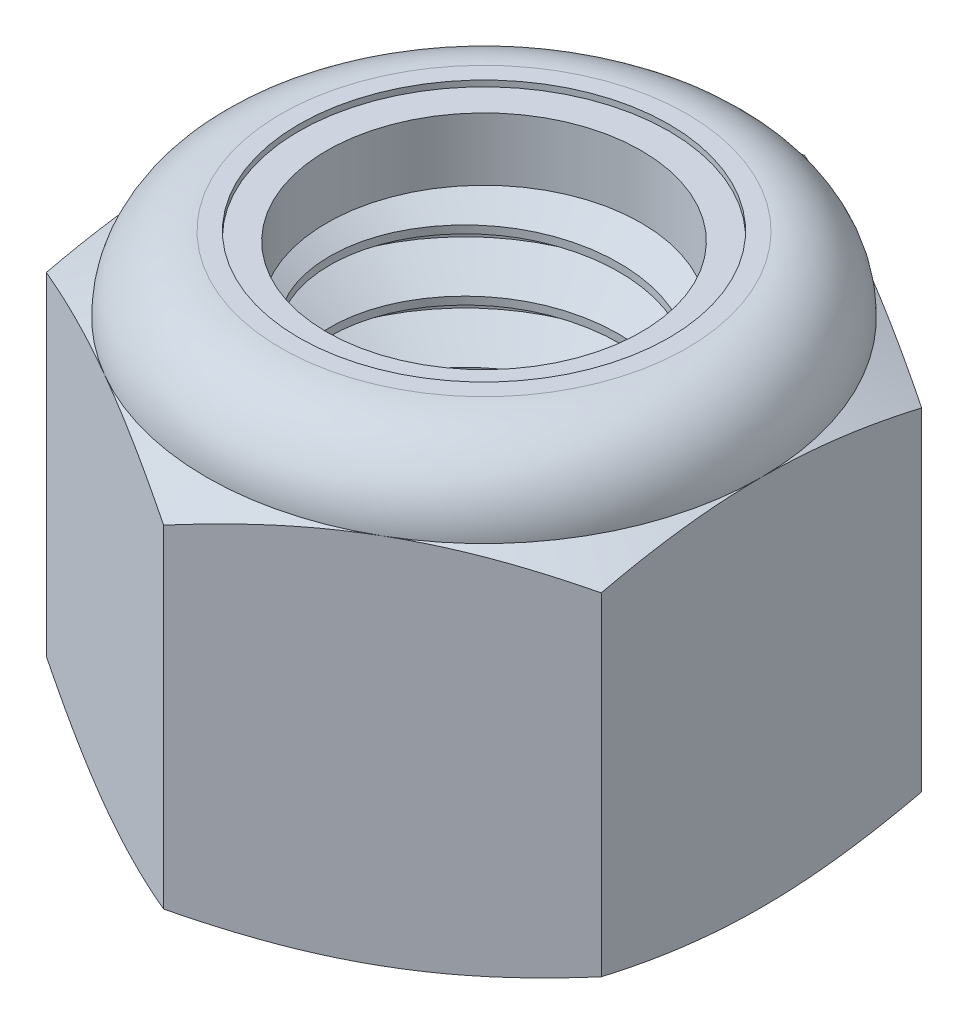
SolidWorks part; units mm, degrees
note: '?' marks a value the reader was unsure of.
ref_plane "Front" through (0, 0, 0) normal (0, 0, 1) x (1, 0, 0)
ref_plane "Top" through (0, 0, 0) normal (0, 1, 0) x (1, 0, 0)
ref_plane "Right" through (0, 0, 0) normal (1, 0, 0) x (0, 0, -1)
sketch "Sketch8" plane through (0, 0, 0) normal (1, 0, 0) x (0, 0, -1)
  line L0 (0, 0) -> (0, 11.5094) construction
  line L1 (7.1437, 0) -> (-7.1437, 0) construction
  line L2 (-4.7625, 11.5094) -> (4.7625, 11.5094) construction
  line L3 (4.7625, 11.5094) -> (4.7625, 9.9219) construction
sketch "Sketch1" plane through (0, 0, 0) normal (0, 1, 0) x (1, 0, 0)
  line L1 (0, 8.2489) -> (-7.1438, 4.1244)
  line L2 (-7.1438, 4.1244) -> (-7.1437, -4.1244)
  line L3 (-7.1437, -4.1244) -> (0, -8.2489)
  line L4 (0, -8.2489) -> (7.1438, -4.1244)
  line L5 (7.1438, -4.1244) -> (7.1438, 4.1244)
  line L6 (7.1438, 4.1244) -> (0, 8.2489)
  circle A0 centre (0, 0) radius 7.1438 construction
  circle A1 centre (0, 0) radius 4.7625
extrude "Extrude1" add sketch "Sketch1" along normal up to vertex (11.5094 mm away) up to point (0, 11.5094, 0)
sketch "Sketch5" plane through (0, 0, 0) normal (1, 0, 0) x (0, 0, -1)
  line L0 (0, 0) -> (7.1437, 0)
  line L1 (7.1437, 0) -> (8.2489, 0.5153)
  line L2 (8.2489, 0.5153) -> (8.2489, 9.0758)
  line L3 (8.2489, 9.0758) -> (7.1437, 9.5911)
  line L4 (5.2255, 11.5094) -> (5.2255, 12.7794)
  line L5 (5.2255, 12.7794) -> (9.5189, 12.7794)
  line L6 (9.5189, 12.7794) -> (9.5189, -1.27)
  line L7 (9.5189, -1.27) -> (0, -1.27)
  line L8 (0, -1.27) -> (0, 0)
  line L9 (7.1437, 9.5911) -> (7.1437, 0) construction
  line L12 (8.2489, 11.5094) -> (8.2489, 0) construction
  line L13 (8.2489, 5.7547) -> (9.5189, 5.7547) construction
  line L15 (0, 0) -> (0, 12.7794) construction
  line L18 (7.1437, 0) -> (-7.1437, 0) construction
  line L19 (4.1244, 11.5094) -> (8.2489, 11.5094) construction
  line L20 (0, 12.7794) -> (5.2255, 12.7794) construction
  line L21 (4.1244, 0) -> (8.2489, 0) construction
  arc A0 (7.1437, 9.5911) -> (5.2255, 11.5094) centre (5.2255, 9.5911) ccw
  dimension "D1" = 25
  dimension "D2" = 1.27
  dimension "D4" = 1.9182
revolve "Cut-Revolve3" cut sketch "Sketch5" angle 360 about L15
sketch "Sketch4" plane through (0, 0, 0) normal (1, 0, 0) x (0, 0, -1)
  line L0 (0, 9.5911) -> (5.2388, 9.5911)
  line L1 (5.2388, 9.5911) -> (0, 7.1483)
  line L3 (0, 2.4429) -> (5.2388, 0)
  line L4 (5.2388, 0) -> (0, 0)
  line L5 (0, 0) -> (0, 9.5911) construction
  line L10 (0, 0) -> (0, 11.5094) construction
  line L11 (0, 2.4429) -> (0, 0)
  line L12 (0, 9.5911) -> (0, 7.1483)
  line L13 (6.1867, 9.5911) -> (0, 9.5911) construction
  dimension "D1" = 25
  dimension "D2" = 10.4775
sketch "Sketch6" plane through (0, 0, 0) normal (1, 0, 0) x (0, 0, -1)
  line L0 (0, 9.5911) -> (6.9913, 9.5911)
  line L1 (5.2255, 11.357) -> (2.6128, 11.357)
  line L2 (0, 12.7794) -> (0, 9.5911)
  line L3 (2.6128, 12.7794) -> (0, 12.7794)
  line L4 (0, 12.7794) -> (5.2255, 12.7794) construction
  line L5 (0, 0) -> (0, 12.7794) construction
  line L6 (0, 12.7794) -> (0, 0) construction
  line L7 (2.6128, 11.357) -> (2.6128, 12.7794)
  line L8 (5.2255, 11.5094) -> (5.2255, 11.357) construction
  line L9 (2.6128, 11.357) -> (0, 11.357) construction
  line L10 (0, 11.357) -> (0, 7.1483) construction
  arc A0 (6.9913, 9.5911) -> (5.2255, 11.357) centre (5.2255, 9.5911) ccw
  arc A1 (7.1437, 9.5911) -> (5.2255, 11.5094) centre (5.2255, 9.5911) ccw construction
  dimension "D1" = 0.1524
revolve "Cut-Revolve4" cut sketch "Sketch6" angle 360 about L6
revolve "Cut-Revolve2" cut sketch "Sketch4" angle 360 about L5
sketch "Sketch7" plane through (0, 0, 0) normal (1, 0, 0) x (0, 0, -1)
  line L0 (4.0481, 9.6673) -> (6.9134, 9.6673)
  line L1 (5.2255, 11.2808) -> (4.0481, 11.2808)
  line L2 (4.0481, 11.2808) -> (4.0481, 9.6673)
  line L3 (4.0481, 9.6673) -> (0, 9.6673) construction
  line L4 (0, 9.6673) -> (0, 11.2808) construction
  line L5 (0, 11.2808) -> (4.0481, 11.2808) construction
  line L6 (4.0481, 9.6673) -> (4.0481, 9.5911) construction
  line L7 (0, 9.5911) -> (6.9913, 9.5911) construction
  line L8 (5.2255, 11.2808) -> (5.2255, 11.357) construction
  arc A0 (6.9134, 9.6673) -> (5.2255, 11.2808) centre (5.2255, 9.5911) ccw
  arc A2 (6.9913, 9.5911) -> (5.2255, 11.357) centre (5.2255, 9.5911) ccw construction
  dimension "D1" = 0.0762
  dimension "D2" = 8.0963
revolve "Revolve2" add sketch "Sketch7" angle 360 about L4
sketch "Sketch2" plane through (0, 0, 0) normal (1, 0, 0) x (0, 0, -1)
  line L0 (-4.7625, 0) -> (-4.7625, 9.5911) construction
  line L1 (0, 0) -> (4.7625, 0)
  line L2 (0, 0) -> (0, 9.5911)
  line L3 (0, 9.5911) -> (4.7625, 9.5911)
  line L4 (4.7625, 0) -> (4.7625, 9.5911)
  line L6 (6.1867, 9.5911) -> (7.1437, 9.5911) construction
  line L7 (0, -4.7625) -> (0, 0) construction
revolve "Revolve1" add sketch "Sketch2" angle 360 about L7
sketch "Sketch9" plane through (0, 0, 0) normal (1, 0, 0) x (0, 0, -1)
  line L0 (4.9344, 11.0794) -> (4.9344, 9.4919) construction
  line L1 (4.9344, 9.4919) -> (3.5595, 10.2857) construction
  line L2 (3.5595, 10.2857) -> (4.9344, 11.0794) construction
  line L3 (3.7314, 10.3849) -> (3.7314, 10.1865) construction
  line L4 (4.7625, 10.9802) -> (4.7625, 9.5911) construction
  line L5 (3.5595, 10.2857) -> (3.7314, 10.2857) construction
  line L6 (4.7625, 10.2857) -> (4.9344, 10.2857) construction
  line L7 (4.8484, 10.2857) -> (4.8484, 11.0298) construction
  line L8 (4.9344, 9.4919) -> (4.8484, 11.0298)
  line L9 (4.8484, 11.0298) -> (3.7314, 10.3849)
  line L10 (3.7314, 10.3849) -> (3.7314, 10.1865)
  line L11 (3.7314, 10.1865) -> (4.9344, 9.4919)
  dimension "D1" = 1.5875
  dimension "D2" = 0.1984
sketch "Sketch10" plane through (0, 9.5911, 0) normal (0, 1, 0) x (1, 0, 0)
  circle A1 centre (0, 0) radius 4.7625
  circle A2 centre (0, 0) radius 4.7625
  dimension "D1" = 0
curve "Helix/Spiral1" pitch 1.5875 height 13.0969 turns 8.25
sweep "Cut-Sweep1" cut profiles "Sketch9" path "Helix/Spiral1" align with end faces yes
sketch "Sketch11" plane through (0, 0, 0) normal (1, 0, 0) x (0, 0, -1)
  line L0 (0, 0) -> (0, 11.5094) construction
  line L1 (7.1437, 0) -> (-7.1437, 0) construction
  line L4 (0, 11.5094) -> (0, 0) construction
  line L5 (0, 5.7547) -> (4.7625, 5.7547) construction
  line L6 (0, 0) -> (5.2388, 0)
  line L7 (0, 2.4429) -> (0, 0)
  line L8 (5.2388, 0) -> (0, 2.4429)
  dimension "D1" = 10.4775
  dimension "D2" = 25
revolve "Revolve3" add sketch "Sketch11" angle 360 about L4
sketch "Sketch12" plane through (0, 0, 0) normal (1, 0, 0) x (0, 0, -1)
  line L0 (5.2388, 9.5911) -> (0, 9.5911)
  line L1 (0, 9.5911) -> (0, 0)
  line L2 (0, 0) -> (5.2388, 0)
  line L3 (7.1437, 0) -> (-7.1437, 0) construction
  line L4 (5.2388, 0) -> (5.2388, 9.5911)
  line L5 (-5.2388, 0) -> (5.2388, 0) construction
revolve "Revolve4" add sketch "Sketch12" angle 360 about L0
combine bodies "Combine1" operation type subtract main body 136 bodies to subtract 133
ref_plane "Contact Plane 1" through (0, 0, 0) normal (0, -1, 0) x (1, 0, 0)
ref_axis "Center Axis 1" through (0, -2.1015, 0) along (0, 1, 0)?
equation "\"D4@Sketch5\"=\"Height@Sketch8\"/6"
equation "\"D1@Sketch9\"=\"Thread Pitch@Sketch8\""
equation "\"D2@Sketch9\"=\"Thread Pitch@Sketch8\"/8"
equation "\"D4@Helix/Spiral1\"=\"Thread Pitch@Sketch8\""
equation "\"D3@Helix/Spiral1\"=\"Thread Pitch@Sketch8\"+\"Height@Sketch8\""
equation "\"D2@Sketch4\"=\"Thread Dia@Sketch8\"*1.1"
equation "\"D1@Sketch11\"=\"Thread Dia@Sketch8\"*1.1"
equation "\"D2@Sketch7\"=\"Thread Dia@Sketch8\"*.85"
